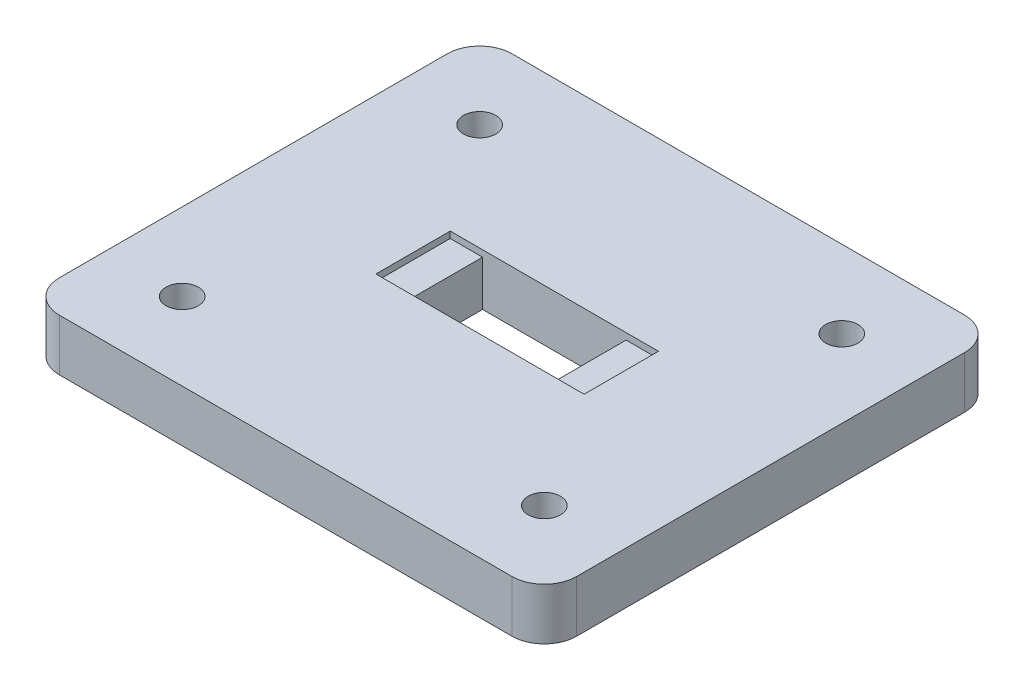
SolidWorks part; units mm, degrees
ref_plane "Front Plane" through (0, 0, 0) normal (0, 0, 1) x (1, 0, 0)
ref_plane "Top Plane" through (0, 0, 0) normal (0, 1, 0) x (1, 0, 0)
ref_plane "Right Plane" through (0, 0, 0) normal (1, 0, 0) x (0, 0, -1)
sketch "Sketch1" plane through (0, 0, 0) normal (0, 1, 0) x (1, 0, 0)
  line L1 (-40, 35) -> (40, 35)
  line L2 (-40, 35) -> (-40, -35)
  line L3 (-40, -35) -> (40, -35)
  line L4 (40, 35) -> (40, -35)
  line L5 (-40, 35) -> (40, -35) construction
  line L6 (-40, -35) -> (40, 35) construction
  point P0 (0, 0)
  dimension "D1" = 80
  dimension "D2" = 70
extrude "Boss-Extrude1" add sketch "Sketch1" along normal blind 8
sketch "Sketch2" plane through (0, 8, 0) normal (0, 1, 0) x (1, 0, 0)
  line L0 (11.166, 0.7324) -> (11.166, 6.4824)
  line L1 (11.166, -5.0176) -> (5.416, -5.0176)
  line L2 (5.416, -5.0176) -> (-11.034, -5.0176)
  line L3 (11.166, 6.4824) -> (11.166, -5.0176)
  line L4 (11.166, -5.0176) -> (11.166, 0.7324)
  line L5 (16.166, -5.0176) -> (11.166, -5.0176)
  line L6 (16.166, 6.4824) -> (16.166, -5.0176)
  line L7 (16.166, 6.4824) -> (11.166, 6.4824)
  line L8 (11.166, 6.4824) -> (5.416, 6.4824)
  line L9 (5.416, 6.4824) -> (-11.034, 6.4824)
  line L10 (-11.034, -5.0176) -> (-11.034, 6.4824)
  line L11 (-16.034, -5.0176) -> (-11.034, -5.0176)
  line L12 (-16.034, 6.4824) -> (-11.034, 6.4824)
  line L13 (-16.034, 6.4824) -> (-16.034, -5.0176)
  arc A0 (0.0073, 2.684) -> (0.0073, -1.2192) centre (-0.584, 0.7324) ccw
  circle A1 centre (5.416, 0.7324) radius 2.25
  arc A2 (0.0073, 2.684) -> (0.0073, -1.2192) centre (-0.584, 0.7324) ccw
  arc A3 (0.0073, -1.2192) -> (0.0073, 2.684) centre (5.416, 0.7324) ccw
  arc A4 (11.166, 0.7324) -> (5.416, 6.4824) centre (5.416, 0.7324) ccw
  circle A5 centre (14.166, 0.7324) radius 1.25
  circle A6 centre (-14.034, 0.7324) radius 1.25
fillet "Fillet1" radius 5 4 edges at (40, 4, 35) (-40, 4, 35) (-40, 4, -35) (40, 4, -35)
extrude "Cut-Extrude1" cut sketch "Sketch2" against normal blind 18 and the other way through all contours A3 L9 L10 L2 A0 | A3 A0 A1 | A1 | A3 L0 L8 | A3 L1 L3 region at (9.8816, 8, -5.198) region at (9.8816, 8, 3.7332) region at (9.3549, 8, 3.2065) region at (-5.2304, 8, -0.7324) region at (5.416, 8, -0.7324)
extrude "Cut-Extrude2" cut sketch "Sketch2<3>" against normal blind 1 and the other way through all contours L6 L7 L0 L3 L5 A5 | A5 | L12 L13 L11 L10 A6 | A6 region at (11.2914, 8, -3.6074) region at (-13.534, 8, 4.8922) region at (14.166, 8, -0.7324) region at (-14.034, 8, -0.7324)
sketch "Sketch2<3>" plane through (0, 8, 0) normal (0, 1, 0) x (1, 0, 0) same geometry as "Sketch2"
sketch "Sketch3" plane through (0, 8, 0) normal (0, 1, 0) x (1, 0, 0)
  line L0 (-61.3667, 0) -> (78.329, 0) construction
  line L1 (0, 40.1909) -> (0, -43.324) construction
  line L2 (40, -30) -> (40, 30) construction
  line L3 (35, 35) -> (-35, 35) construction
  circle A0 centre (28, 23) radius 2.5
  circle A1 centre (28, -23) radius 2.5
  circle A2 centre (-28, 23) radius 2.5
  circle A3 centre (-28, -23) radius 2.5
  dimension "D1" = 5
  dimension "D2" = 12
  dimension "D3" = 12
extrude "Cut-Extrude3" cut sketch "Sketch3" against normal blind 31
